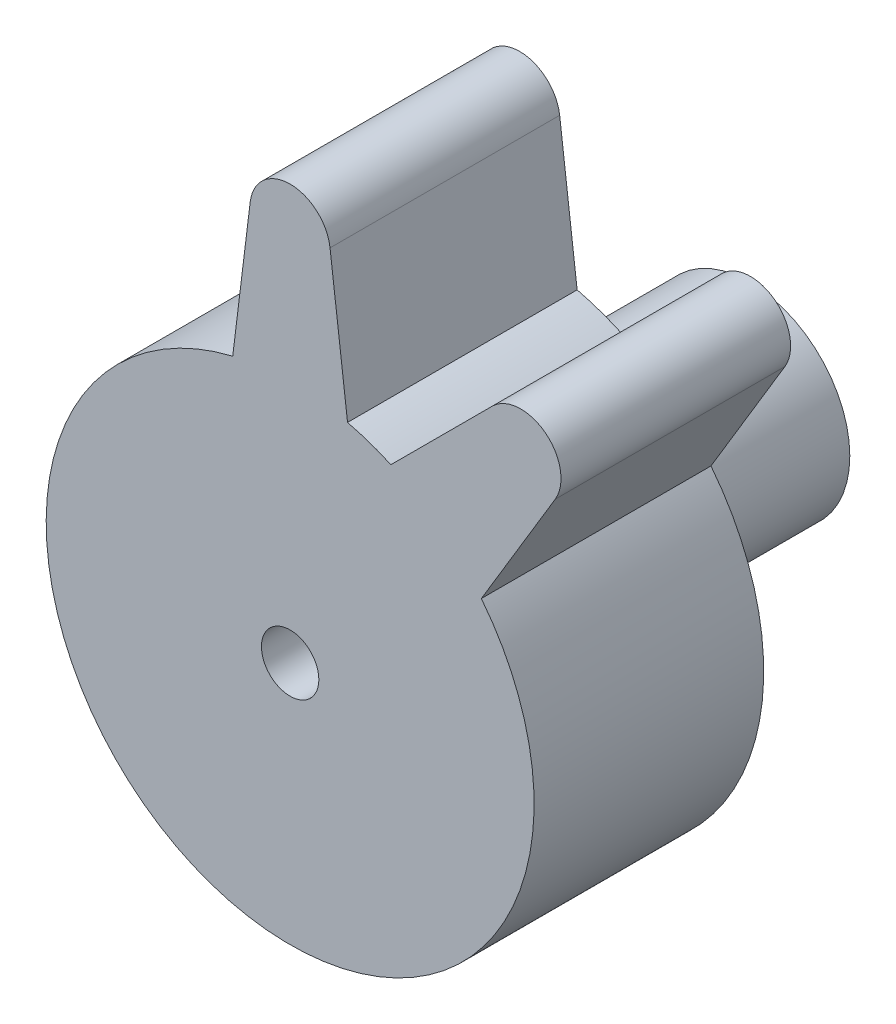
SolidWorks part; units mm, degrees
ref_plane "Front Plane" through (0, 0, 0) normal (0, 0, 1) x (1, 0, 0)
ref_plane "Top Plane" through (0, 0, 0) normal (0, 1, 0) x (1, 0, 0)
ref_plane "Right Plane" through (0, 0, 0) normal (1, 0, 0) x (0, 0, -1)
sketch "Sketch1" plane through (0, 0, 0) normal (0, 0, 1) x (1, 0, 0)
  line L0 (0, 0) -> (0, 51.188) construction
  line L1 (-2, 8.2614) -> (-1.3907, 13.2241)
  line L2 (2, 8.2614) -> (1.3907, 13.2241)
  line L3 (0, 0) -> (22.4184, 65.1077) construction
  line L4 (6.6622, 5.2787) -> (9.2374, 9.5646)
  line L5 (0, 0) -> (31.5145, 40.3367) construction
  line L6 (3.5102, 7.7414) -> (7.0457, 11.2769)
  circle A0 centre (0, 0) radius 8.5
  circle A1 centre (0, 0) radius 1
  arc A2 (-1.3907, 13.2241) -> (1.3907, 13.2241) centre (0, 13.0533) cw
  arc A3 (9.2374, 9.5646) -> (7.0457, 11.2769) centre (8.0364, 10.2862) ccw
  circle A4 centre (0, 0) radius 12 construction
  dimension "D1" = 24
  dimension "D2" = 17
  dimension "D3" = 2
  dimension "D4" = 7
  dimension "D7" = 5
  dimension "D5" = 4
  dimension "D6" = 19
extrude "Boss-Extrude1" add sketch "Sketch1" along normal blind 8 contours A0 A1 | A2 L1 A0 L2 | A0 region at (0, 11.1065, 0) region at (0, 8.2596, 0) region at (6.8378, 8.752, 0)
sketch "Sketch5" plane through (0, 0, 0) normal (0, 0, -1) x (-1, 0, 0)
  line L0 (1.3229, -1.5) -> (1.3229, 1.5)
  line L1 (3.1623, -1.5) -> (3.1623, 1.5)
  circle A0 centre (0, 0) radius 2
  circle A1 centre (0, 0) radius 3.5
  arc M7 (-2, 8.2614) -> (-3.5102, 7.7414) centre (0, 0) ccw
  dimension "D1" = 7
  dimension "D2" = 4
  dimension "D3" = 3
  dimension "D4" = 3
extrude "Boss-Extrude3" add sketch "Sketch5" along normal blind 8 contours L0 A0 | A1 A0 M7 region at (-1.5981, 0, 0) region at (3.4034, 0, 0)
sketch "Sketch6" plane through (-3.1623, 0, 0) normal (-1, 0, 0) x (0, 0, 1)
  line L0 (-8, -1.5) -> (-8, 1.5) construction
  circle A0 centre (-5, 0) radius 1
  point P2 (0, 0)
  point P3 (-4.5023, 0)
  point P6 (0, 0)
  point P9 (0, 0)
  dimension "D1" = 2
  dimension "D2" = 3
extrude "Cut-Extrude1" cut sketch "Sketch6" against normal blind 2
